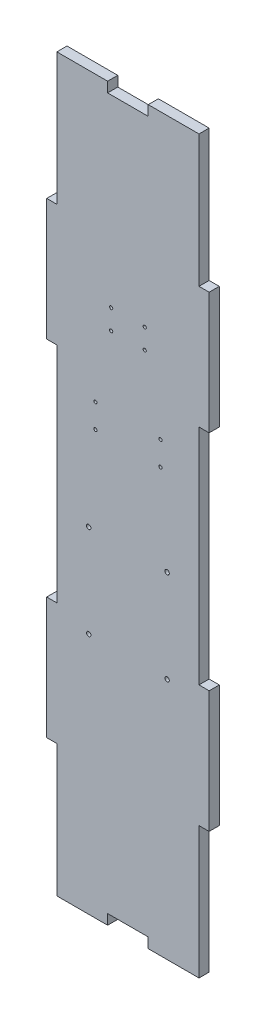
SolidWorks part; units mm, degrees
ref_plane "Front Plane" through (0, 0, 0) normal (0, 0, 1) x (1, 0, 0)
ref_plane "Top Plane" through (0, 0, 0) normal (0, 1, 0) x (1, 0, 0)
ref_plane "Right Plane" through (0, 0, 0) normal (1, 0, 0) x (0, 0, -1)
sketch "Sketch1" plane through (0, 0, 0) normal (0, 0, 1) x (1, 0, 0)
  line L1 (-192.6077, 179.9617) -> (-103.7077, 179.9617)
  line L2 (-192.6077, 179.9617) -> (-192.6077, -277.2383)
  line L3 (-192.6077, -277.2383) -> (-103.7077, -277.2383)
  line L4 (-103.7077, 179.9617) -> (-103.7077, -277.2383)
  dimension "D1" = 457.2
  dimension "D2" = 88.9
extrude "Boss-Extrude1" add sketch "Sketch1" along normal blind 6.35
sketch "Sketch2" plane through (0, 0, 6.35) normal (0, 0, 1) x (1, 0, 0)
  line L0 (-192.6077, 179.9617) -> (-192.6077, -277.2383) construction
  line L1 (-198.9577, 97.4117) -> (-192.6077, 97.4117)
  line L2 (-198.9577, 97.4117) -> (-198.9577, 21.2117)
  line L3 (-198.9577, 21.2117) -> (-192.6077, 21.2117)
  line L4 (-192.6077, 97.4117) -> (-192.6077, 21.2117)
  line L6 (-198.9577, -118.4883) -> (-192.6077, -118.4883)
  line L7 (-198.9577, -118.4883) -> (-198.9577, -194.6883)
  line L8 (-198.9577, -194.6883) -> (-192.6077, -194.6883)
  line L9 (-192.6077, -118.4883) -> (-192.6077, -194.6883)
  line L10 (-148.1577, 179.9617) -> (-148.1577, -277.2383) construction
  line L11 (-103.7077, 179.9617) -> (-192.6077, 179.9617) construction
  line L12 (-192.6077, -277.2383) -> (-103.7077, -277.2383) construction
  line L13 (-97.3577, -194.6883) -> (-103.7077, -194.6883)
  line L14 (-97.3577, -118.4883) -> (-97.3577, -194.6883)
  line L15 (-103.7077, -118.4883) -> (-103.7077, -194.6883)
  line L16 (-97.3577, -118.4883) -> (-103.7077, -118.4883)
  line L17 (-97.3577, 21.2117) -> (-103.7077, 21.2117)
  line L18 (-97.3577, 97.4117) -> (-97.3577, 21.2117)
  line L19 (-103.7077, 97.4117) -> (-103.7077, 21.2117)
  line L20 (-97.3577, 97.4117) -> (-103.7077, 97.4117)
  dimension "D1" = 82.55
  dimension "D4" = 82.55
  dimension "D5" = 6.35
extrude "Boss-Extrude4" add sketch "Sketch2" against normal through all
sketch "Sketch3" plane through (0, 0, 6.35) normal (0, 0, 1) x (1, 0, 0)
  line L0 (-192.6077, -277.2383) -> (-103.7077, -277.2383) construction
  line L1 (-160.8577, -277.2383) -> (-135.4577, -277.2383)
  line L2 (-160.8577, -277.2383) -> (-160.8577, -270.8883)
  line L3 (-160.8577, -270.8883) -> (-135.4577, -270.8883)
  line L4 (-135.4577, -277.2383) -> (-135.4577, -270.8883)
  line L5 (-148.1577, 179.9617) -> (-148.1577, -277.2383) construction
  line L6 (-103.7077, 179.9617) -> (-192.6077, 179.9617) construction
  line L7 (-192.6077, -194.6883) -> (-192.6077, -277.2383) construction
  line L11 (-103.7077, 97.4117) -> (-103.7077, 179.9617) construction
  line L12 (-160.8577, 179.9617) -> (-135.4577, 179.9617)
  line L13 (-160.8577, 179.9617) -> (-160.8577, 173.6117)
  line L14 (-160.8577, 173.6117) -> (-135.4577, 173.6117)
  line L15 (-135.4577, 179.9617) -> (-135.4577, 173.6117)
  dimension "D5" = 6.35
  dimension "D2" = 25.4
  dimension "D3" = 6.35
  dimension "D4" = 25.4
  dimension "D6" = 31.75
  dimension "D1" = 31.75
extrude "Cut-Extrude1" cut sketch "Sketch3" against normal blind 6.35
sketch "Sketch4" plane through (0, 0, 0) normal (0, 0, 1) x (1, 0, 0)
  line L0 (-192.6077, -277.2383) -> (-160.8577, -277.2383) construction
  line L1 (-175.6577, -65.2383) -> (-120.6577, -65.2383) construction
  line L2 (-175.6577, -65.2383) -> (-175.6577, -150.2383) construction
  line L3 (-175.6577, -150.2383) -> (-120.6577, -150.2383) construction
  line L4 (-120.6577, -65.2383) -> (-120.6577, -150.2383) construction
  line L5 (-148.1577, -65.2383) -> (-148.1577, -150.2383) construction
  line L6 (-175.6577, -107.7383) -> (-120.6577, -107.7383) construction
  line L7 (-103.7077, -118.4883) -> (-103.7077, 21.2117) construction
  line L8 (-160.6355, 60.3617) -> (-135.6355, 60.3617) construction
  line L9 (-160.6355, 60.3617) -> (-160.6355, 36.3617) construction
  line L10 (-160.6355, 36.3617) -> (-135.6355, 36.3617) construction
  line L11 (-135.6355, 60.3617) -> (-135.6355, 36.3617) construction
  line L12 (-148.1577, 173.6117) -> (-148.1577, -270.8883) construction
  line L13 (-160.8577, 173.6117) -> (-135.4577, 173.6117) construction
  line L14 (-135.4577, -270.8883) -> (-160.8577, -270.8883) construction
  line L15 (-148.1577, 4.9389) -> (-148.1577, -15.0611) construction
  line L16 (-171.0177, 4.9389) -> (-125.2977, 4.9389) construction
  line L17 (-171.0177, 4.9389) -> (-171.0177, -15.0611) construction
  line L18 (-171.0177, -15.0611) -> (-125.2977, -15.0611) construction
  line L19 (-125.2977, 4.9389) -> (-125.2977, -15.0611) construction
  line L20 (-171.0177, -5.0611) -> (-125.2977, -5.0611) construction
  line L21 (-135.4577, -277.2383) -> (-103.7077, -277.2383) construction
  circle A0 centre (-172.6577, -67.3936) radius 1.375
  circle A1 centre (-123.6577, -67.3936) radius 1.375
  circle A2 centre (-123.6576, -125.3936) radius 1.375
  circle A3 centre (-172.6577, -125.3936) radius 1.375
  circle A4 centre (-158.6355, 58.3617) radius 1
  circle A5 centre (-158.6355, 45.8617) radius 1
  circle A6 centre (-137.6355, 58.3617) radius 1
  circle A7 centre (-137.6355, 45.8617) radius 1
  circle A8 centre (-168.5177, 2.4389) radius 1
  circle A9 centre (-127.7977, 2.4389) radius 1
  circle A10 centre (-127.7977, -12.5611) radius 1
  circle A11 centre (-168.5177, -12.5611) radius 1
  dimension "D5" = 2.75
  dimension "D4" = 2.75
  dimension "D9" = 2
  dimension "D23" = 2
  dimension "D1" = 127
  dimension "D2" = 85
  dimension "D3" = 55
  dimension "D6" = 58
  dimension "D7" = 25
  dimension "D8" = 24
  dimension "D10" = 21
  dimension "D11" = 12.5
  dimension "D12" = 9.5
  dimension "D13" = 2
  dimension "D14" = 2
  dimension "D15" = 2
  dimension "D16" = 31.9278
  dimension "D17" = 101.6
  dimension "D18" = 0
  dimension "D19" = 49
  dimension "D20" = 20
  dimension "D21" = 45.72
  dimension "D22" = 0
  dimension "D24" = 2.5
  dimension "D25" = 2.5
extrude "Cut-Extrude5" cut sketch "Sketch4" against normal through all and the other way through all
equation "\"width\"= 3.5in"
equation "\"Height\"= 18in"
equation "\"thick\"= 0.25"
equation "\"D1@Sketch1\"=\"Height\""
equation "\"D2@Sketch1\"=\"width\""
equation "\"D1@Boss-Extrude1\"=\"thick\""
equation "\"D5@Sketch2\"=\"thick\""
equation "\"D1\"= \"thick\""
equation "\"D3@Sketch3\"=\"thick\""
equation "\"D1@Cut-Extrude1\"=\"thick\""
equation "\"D5@Sketch3\"=\"thick\""
equation "\"D2@Cut-Extrude5\"=\"thick\""
